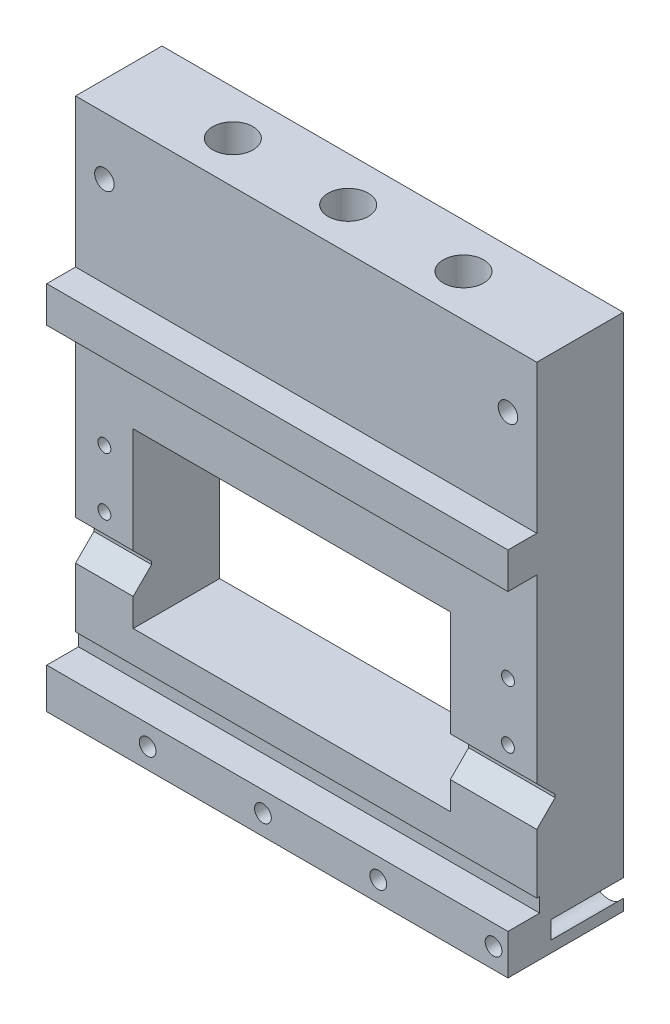
SolidWorks part; units mm, degrees
material "ABS"
ref_plane "Front Plane" through (0, 0, 0) normal (0, 0, 1) x (1, 0, 0)
ref_plane "Top Plane" through (0, 0, 0) normal (0, 1, 0) x (1, 0, 0)
ref_plane "Right Plane" through (0, 0, 0) normal (1, 0, 0) x (0, 0, -1)
sketch "Sketch1" plane through (0, 0, 0) normal (0, 0, 1) x (1, 0, 0)
  line L1 (-83.1034, 136.2931) -> (76.8966, 136.2931)
  line L2 (-83.1034, 136.2931) -> (-83.1034, -43.7069)
  line L3 (-83.1034, -43.7069) -> (76.8966, -43.7069)
  line L4 (76.8966, 136.2931) -> (76.8966, -43.7069)
  line L5 (-63.1034, 46.2931) -> (46.8966, 46.2931)
  line L6 (-63.1034, 46.2931) -> (-63.1034, -13.7069)
  line L7 (-63.1034, -13.7069) -> (46.8966, -13.7069)
  line L8 (46.8966, 46.2931) -> (46.8966, -13.7069)
  dimension "D1" = 60
  dimension "D2" = 180
  dimension "D3" = 90
  dimension "D4" = 160
  dimension "D5" = 30
  dimension "D6" = 110
extrude "Boss-Extrude1" add sketch "Sketch1" along normal blind 30
sketch "Sketch2" plane through (-83.1034, 0, 0) normal (-1, 0, 0) x (0, 0, 1)
  line L0 (30, 9.6571) -> (23.636, 3.2931)
  line L1 (30, 136.2931) -> (30, -43.7069) construction
  line L2 (23.636, 3.2931) -> (23.636, 2.2931)
  line L3 (23.636, 2.2931) -> (30, -4.0709)
  line L4 (30, -4.0709) -> (30, 9.6571)
  line L5 (30, -43.7069) -> (0, -43.7069) construction
  line L7 (30, -24.7069) -> (29, -24.7069)
  line L8 (30, -24.7069) -> (30, -29.7069)
  line L9 (30, -29.7069) -> (29, -29.7069)
  line L10 (29, -24.7069) -> (29, -29.7069)
  point P13 (29.5, -29.7069)
  dimension "D1" = 9
  dimension "D2" = 9
  dimension "D3" = 1
  dimension "D4" = 47
  dimension "D5" = 135
  dimension "D6" = 90
  dimension "D7" = 5
  dimension "D8" = 14
  dimension "D9" = 1
extrude "Cut-Extrude1" cut sketch "Sketch2" against normal blind 300
sketch "Sketch11" plane through (0, 0, 30) normal (0, 0, 1) x (1, 0, 0)
  line L0 (-83.1034, 136.2931) -> (-83.1034, 9.6571) construction
  line L1 (-83.1034, -29.7069) -> (76.8966, -29.7069)
  line L2 (-83.1034, -29.7069) -> (-83.1034, -43.7069)
  line L3 (-83.1034, -43.7069) -> (76.8966, -43.7069)
  line L4 (76.8966, -29.7069) -> (76.8966, -43.7069)
  line L5 (76.8966, 9.6571) -> (76.8966, 136.2931) construction
  line L6 (-83.1034, -43.7069) -> (76.8966, -43.7069) construction
  line L7 (76.8966, 84.8931) -> (-83.1034, 84.8931)
  line L8 (76.8966, 84.8931) -> (76.8966, 72.3931)
  line L9 (76.8966, 72.3931) -> (-83.1034, 72.3931)
  line L10 (-83.1034, 84.8931) -> (-83.1034, 72.3931)
  dimension "D1" = 14
  dimension "D2" = 12.5
  dimension "D3" = 128.6
extrude "Boss-Extrude2" add sketch "Sketch11" along normal blind 10
sketch "Sketch3" plane through (0, 136.2931, 0) normal (0, 1, 0) x (1, 0, 0)
  line L0 (-83.1034, -30) -> (-83.1034, 0) construction
  circle A0 centre (-43.1034, -15.4362) radius 3
  dimension "D1" = 40
extrude "Cut-Extrude2" cut sketch "Sketch3" against normal blind 100
sketch "Sketch4" plane through (0, 136.2931, 0) normal (0, 1, 0) x (1, 0, 0)
  circle A0 centre (-43.1034, -15.4362) radius 7
  circle A1 centre (-43.1034, -15.4362) radius 3 construction
extrude "Cut-Extrude3" cut sketch "Sketch4" against normal blind 70
pattern_linear "LPattern1" count 3 spacing 40 along (1, 0, 0) of "Cut-Extrude2", "Cut-Extrude3"
sketch "Sketch5" plane through (0, 0, 0) normal (0, 0, -1) x (-1, 0, 0)
  line L0 (83.1034, 136.2931) -> (83.1034, -43.7069) construction
  line L1 (63.1034, -13.7069) -> (-46.8966, -13.7069) construction
  circle A0 centre (73.1034, 16.2931) radius 2.2387
  dimension "D1" = 10
  dimension "D2" = 30
extrude "Cut-Extrude4" cut sketch "Sketch5" against normal blind 100
sketch "Sketch6" plane through (0, 0, 0) normal (0, 0, -1) x (-1, 0, 0)
  circle A0 centre (73.1034, 16.2931) radius 4.369
extrude "Cut-Extrude5" cut sketch "Sketch6" against normal blind 25
pattern_linear "LPattern2" count 2 spacing 20 along (0, 1, 0) count 2 spacing 140 along (1, 0, 0) of "Cut-Extrude4", "Cut-Extrude5"
sketch "Sketch9" plane through (0, 0, 0) normal (0, 0, -1) x (-1, 0, 0)
  line L0 (-76.8966, -43.7069) -> (-76.8966, 136.2931) construction
  line L1 (-76.8966, 136.2931) -> (83.1034, 136.2931) construction
  circle A0 centre (-66.8966, 116.2931) radius 3.3818
  dimension "D1" = 10
  dimension "D2" = 20
extrude "Cut-Extrude8" cut sketch "Sketch9" against normal blind 100
sketch "Sketch10" plane through (0, 0, 30) normal (0, 0, 1) x (1, 0, 0)
  circle A0 centre (66.8966, 116.2931) radius 6.9825
  circle A1 centre (66.8966, 116.2931) radius 3.3818 construction
extrude "Cut-Extrude9" cut sketch "Sketch10" against normal blind 20 from offset 10 offset against normal yes
pattern_linear "LPattern4" count 2 spacing 140 along (-1, 0, 0) of "Cut-Extrude9", "Cut-Extrude8"
sketch "Sketch7" plane through (0, 0, 0) normal (0, 0, -1) x (-1, 0, 0)
  line L0 (83.1034, -43.7069) -> (-76.8966, -43.7069) construction
  line L1 (83.1034, 136.2931) -> (83.1034, -43.7069) construction
  circle A0 centre (48.1034, -36.7069) radius 2.9002
  point P2 (47.7929, -35.3996)
  point P5 (63.1034, 89.9987)
  dimension "D1" = 7
  dimension "D2" = 35
extrude "Cut-Extrude6" cut sketch "Sketch7" against normal blind 40
sketch "Sketch8" plane through (0, 0, 0) normal (0, 0, -1) x (-1, 0, 0)
  circle A0 centre (48.1034, -36.7069) radius 5.871
extrude "Cut-Extrude7" cut sketch "Sketch8" against normal blind 25
pattern_linear "Линейный массив1" count 4 spacing 40 along (1, 0, 0) of "Cut-Extrude6", "Cut-Extrude7"
